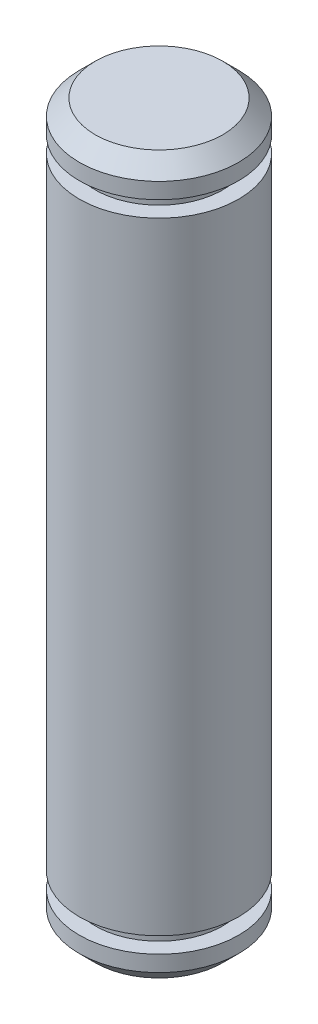
SolidWorks part; units mm, degrees
ref_plane "Front Plane" through (0, 0, 0) normal (0, 0, 1) x (1, 0, 0)
ref_plane "Top Plane" through (0, 0, 0) normal (0, 1, 0) x (1, 0, 0)
ref_plane "Right Plane" through (0, 0, 0) normal (1, 0, 0) x (0, 0, -1)
sketch "Sketch1" plane through (0, 0, 0) normal (0, 1, 0) x (1, 0, 0)
  circle A0 centre (0, 0) radius 5
  dimension "D1" = 10
extrude "Boss-Extrude1" add sketch "Sketch1" along normal blind 45
chamfer "Chamfer1" distance 1 angle 45 2 edges at (0, 45, 5) (0, 0, 5)
sketch "Sketch2" plane through (0, 0, 0) normal (0, -1, 0) x (1, 0, 0)
  circle A0 centre (0, 0) radius 4
  circle A1 centre (0, 0) radius 6
  dimension "D1" = 8
  dimension "D2" = 12
extrude "Cut-Extrude1" cut sketch "Sketch2" against normal blind 1 from offset 2 offset against normal yes
extrude "Cut-Extrude2" cut sketch "Sketch2<2>" against normal blind 1 from offset 42 offset against normal yes
sketch "Sketch2<2>" plane through (0, 0, 0) normal (0, -1, 0) x (1, 0, 0) same geometry as "Sketch2"
